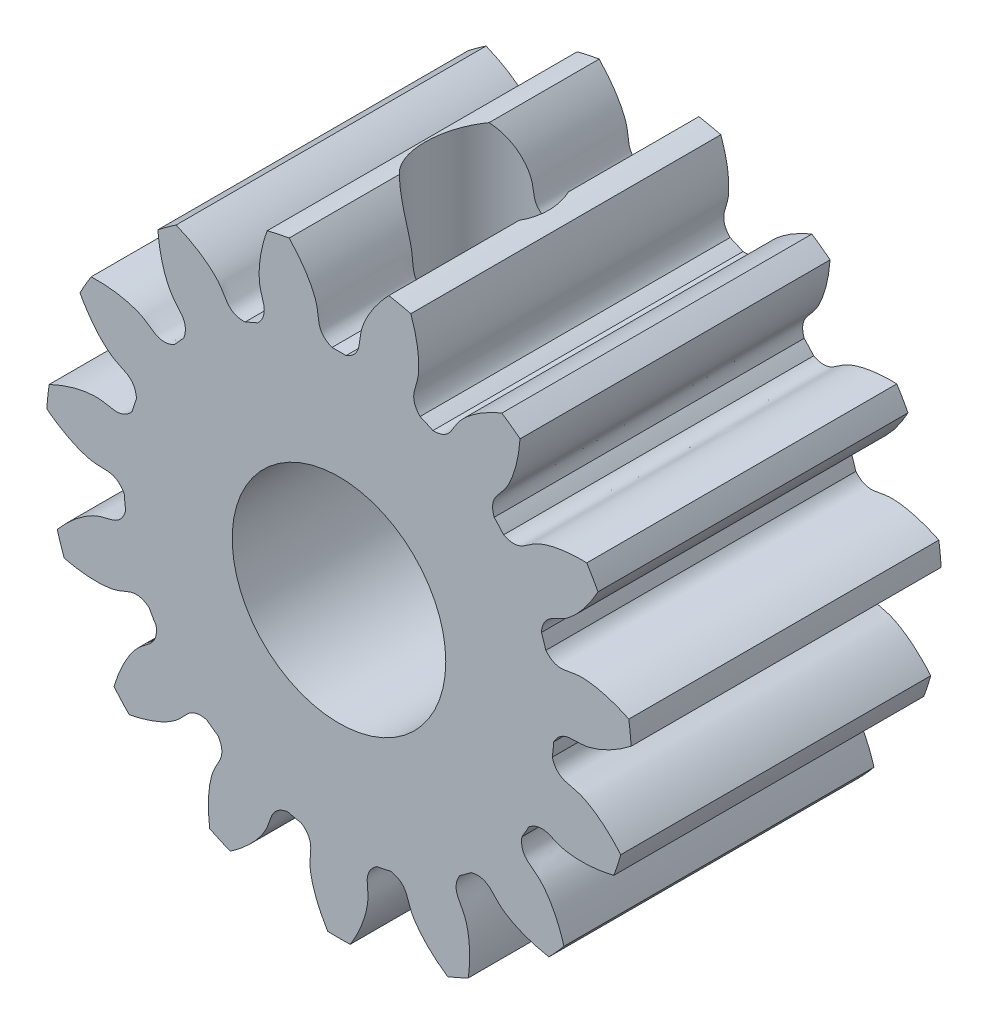
SolidWorks part; units mm, degrees
ref_plane "前视基准面" through (0, 0, 0) normal (0, 0, 1) x (1, 0, 0)
ref_plane "上视基准面" through (0, 0, 0) normal (0, 1, 0) x (1, 0, 0)
ref_plane "右视基准面" through (0, 0, 0) normal (1, 0, 0) x (0, 0, -1)
sketch "草图1" plane through (0, 0, 0) normal (0, 0, 1) x (1, 0, 0)
  circle A0 centre (0, 0) radius 4.25
extrude "凸台-拉伸1" add sketch "草图1" along normal blind 4.5
ref_axis "基准轴1" through (0, 0, 4.5) along (0, 0, -1)
sketch "草图2" plane through (0, 0, 0) normal (0, 0, 1) x (1, 0, 0)
  line L0 (0, 0) -> (0, 4.25) construction
  circle A0 centre (0, 0) radius 4.25 construction
  arc A1 (0.1021, 3.1233) -> (-0.1021, 3.1233) centre (0, 0) ccw
  arc A2 (1.6234, 4.818) -> (-1.6234, 4.818) centre (0, 0) ccw
  spline S0 degree 3 poles (0.1021, 3.1233) (0.3286, 3.2172) (0.2861, 3.3932) (0.3256, 3.5543) (0.3287, 3.5658) (0.3324, 3.5787) (0.3368, 3.5928) (0.3419, 3.6082) (0.3478, 3.6248) (0.3545, 3.6426) (0.3621, 3.6616) (0.3706, 3.6817) (0.3801, 3.703) (0.3906, 3.7253) (0.4022, 3.7486) (0.4149, 3.773) (0.4288, 3.7984) (0.4438, 3.8247) (0.4601, 3.8519) (0.4777, 3.8799) (0.4967, 3.9088) (0.517, 3.9385) (0.5387, 3.9689) (0.5618, 4) (0.5865, 4.0317) (0.6126, 4.064) (0.6403, 4.0969) (0.6696, 4.1303) (0.7005, 4.1641) (0.733, 4.1983) (0.7673, 4.2329) (0.8032, 4.2678) (0.8408, 4.3029) (0.8801, 4.3381) (0.9213, 4.3735) (0.9642, 4.409) (1.0089, 4.4445) (1.0555, 4.4799) (1.1039, 4.5153) (1.1541, 4.5504) (1.2062, 4.5854) (1.2602, 4.62) (1.316, 4.6543) (1.3738, 4.6882) (1.4334, 4.7216) (1.5163, 4.7659) (1.5801, 4.7975) (1.6234, 4.818) knots 0 0 0 0 0.202473 0.206979 0.212085 0.217793 0.224101 0.23101 0.23852 0.24663 0.255341 0.264653 0.274566 0.285079 0.296194 0.307909 0.320225 0.333141 0.346659 0.360777 0.375496 0.390816 0.406736 0.423257 0.440379 0.458102 0.476426 0.49535 0.514875 0.535001 0.555728 0.577055 0.598984 0.621513 0.644642 0.668373 0.692704 0.717636 0.743169 0.769303 0.796037 0.823373 0.851309 0.879845 0.908983 0.938721 1 1 1 1
  spline S1 degree 3 poles (-0.1021, 3.1233) (-0.3286, 3.2172) (-0.2861, 3.3932) (-0.3256, 3.5543) (-0.3287, 3.5658) (-0.3324, 3.5787) (-0.3368, 3.5928) (-0.3419, 3.6082) (-0.3478, 3.6248) (-0.3545, 3.6426) (-0.3621, 3.6616) (-0.3706, 3.6817) (-0.3801, 3.703) (-0.3906, 3.7253) (-0.4022, 3.7486) (-0.4149, 3.773) (-0.4288, 3.7984) (-0.4438, 3.8247) (-0.4601, 3.8519) (-0.4777, 3.8799) (-0.4967, 3.9088) (-0.517, 3.9385) (-0.5387, 3.9689) (-0.5618, 4) (-0.5865, 4.0317) (-0.6126, 4.064) (-0.6403, 4.0969) (-0.6696, 4.1303) (-0.7005, 4.1641) (-0.733, 4.1983) (-0.7673, 4.2329) (-0.8032, 4.2678) (-0.8408, 4.3029) (-0.8801, 4.3381) (-0.9213, 4.3735) (-0.9642, 4.409) (-1.0089, 4.4445) (-1.0555, 4.4799) (-1.1039, 4.5153) (-1.1541, 4.5504) (-1.2062, 4.5854) (-1.2602, 4.62) (-1.316, 4.6543) (-1.3738, 4.6882) (-1.4334, 4.7216) (-1.5163, 4.7659) (-1.5801, 4.7975) (-1.6234, 4.818) knots 0 0 0 0 0.202473 0.206979 0.212085 0.217793 0.224101 0.23101 0.23852 0.24663 0.255341 0.264653 0.274566 0.285079 0.296194 0.307909 0.320225 0.333141 0.346659 0.360777 0.375496 0.390816 0.406736 0.423257 0.440379 0.458102 0.476426 0.49535 0.514875 0.535001 0.555728 0.577055 0.598984 0.621513 0.644642 0.668373 0.692704 0.717636 0.743169 0.769303 0.796037 0.823373 0.851309 0.879845 0.908983 0.938721 1 1 1 1
extrude "切除-拉伸1" cut sketch "草图2" along normal through all
pattern_circular "阵列(圆周)1" count 15 every 24 about axis through (0, 0, 4.5) along (0, 0, -1) of "切除-拉伸1"
sketch "草图3" plane through (0, 0, 0) normal (0, 0, 1) x (1, 0, 0)
  circle A0 centre (0, 0) radius 3.75 construction
  dimension "Dn" = 7.5
sketch "草图4" plane through (0, 0, 4.5) normal (0, 0, 1) x (1, 0, 0)
  circle A0 centre (0, 0) radius 1.55
  dimension "D1" = 3.1
extrude "切除-拉伸2" cut sketch "草图4" against normal up to next
ref_plane "基准面1" through (0, 4.2, 0) normal (0, 1, 0) x (1, 0, 0)
sketch "草图5" plane through (0, 0, 0) normal (0, 1, 0) x (1, 0, 0)
  line L0 (-0.1021, -4.5) -> (-0.1021, 0) construction
  circle A0 centre (-0.1021, -2.25) radius 0.9
  dimension "D1" = 1.8
extrude "切除-拉伸3" cut sketch "草图5" against normal blind 2 from surface starting at plane "基准面1"
sketch "草图6" plane through (0, 2.2, 0) normal (0, 1, 0) x (1, 0, 0)
  circle A0 centre (-0.1021, -2.25) radius 0.5
  dimension "D1" = 1
extrude "切除-拉伸4" cut sketch "草图6" against normal up to next
